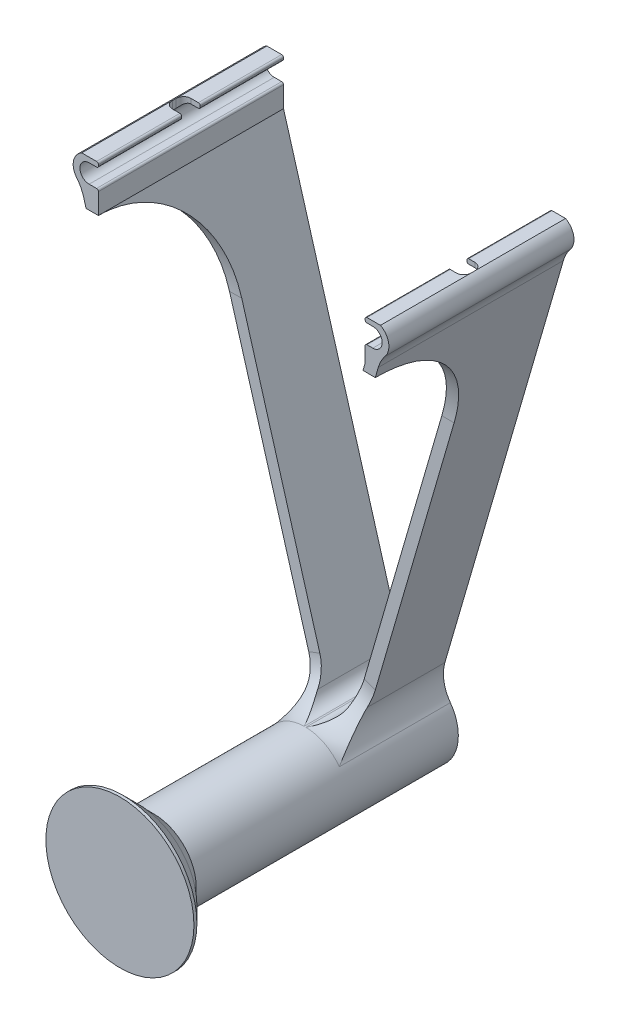
SolidWorks part; units mm, degrees
ref_plane "Front Plane" through (0, 0, 0) normal (0, 0, 1) x (1, 0, 0)
ref_plane "Top Plane" through (0, 0, 0) normal (0, 1, 0) x (1, 0, 0)
ref_plane "Right Plane" through (0, 0, 0) normal (1, 0, 0) x (0, 0, -1)
sketch "Sketch1" plane through (0, 0, 0) normal (0, 0, 1) x (1, 0, 0)
  line L6 (-35.807, 65.4375) -> (-21.497, 16.2472)
  line L8 (36.2341, 66.9059) -> (21.497, 16.2472)
  line L17 (39.7899, 67.7154) -> (18.5233, -5.3886)
  line L18 (-39.8147, 67.8005) -> (-18.5233, -5.3886)
  line L34 (-39.8353, 77.8524) -> (-36.807, 77.8524)
  line L35 (39.8353, 77.8524) -> (40.3798, 77.8524)
  line L36 (-39.8353, 77.8524) -> (-40.307, 77.8524)
  line L40 (36.2341, 77.0752) -> (36.2341, 77.3524)
  line L42 (36.2341, 70.9868) -> (36.2341, 66.9059)
  line L43 (36.7341, 77.8524) -> (39.8353, 77.8524)
  line L45 (-38.307, 71.5312) -> (-36.307, 71.5312)
  line L46 (-35.807, 71.0312) -> (-35.807, 65.4375)
  line L47 (-36.807, 77.8524) -> (-36.307, 77.8524)
  line L48 (-35.807, 77.3524) -> (-35.807, 77.0313)
  line L49 (38.307, 71.4868) -> (36.7341, 71.4868)
  line L50 (-38.307, 76.5313) -> (-36.307, 76.5313)
  line L51 (38.307, 76.5752) -> (36.7341, 76.5752)
  line L52 (-21.497, 16.2472) -> (-4.158, -43.3559)
  line L53 (21.497, 16.2472) -> (4.158, -43.3559)
  line L56 (-18.5233, -5.3886) -> (-7.7737, -42.3405)
  line L57 (7.7737, -42.3405) -> (18.5233, -5.3886)
  arc A10 (-40.307, 77.8524) -> (-41.6546, 71.312) centre (-38.307, 74.0312) ccw
  arc A11 (41.6658, 71.2709) -> (40.3798, 77.8524) centre (38.307, 74.031) ccw
  arc A16 (41.6658, 71.2709) -> (39.7899, 67.7154) centre (49.3919, 64.9221) ccw
  arc A17 (-39.8147, 67.8005) -> (-41.6546, 71.312) centre (-49.4166, 65.0072) ccw
  arc A23 (36.2341, 77.3524) -> (36.7341, 77.8524) centre (36.7341, 77.3524) cw
  arc A24 (-38.307, 76.5313) -> (-38.307, 71.5312) centre (-38.307, 74.0312) ccw
  arc A25 (38.307, 71.4868) -> (38.307, 76.5752) centre (38.307, 74.031) ccw
  arc A26 (-36.307, 71.5312) -> (-35.807, 71.0312) centre (-36.307, 71.0312) cw
  arc A27 (36.7341, 71.4868) -> (36.2341, 70.9868) centre (36.7341, 70.9868) ccw
  arc A28 (36.7341, 76.5752) -> (36.2341, 77.0752) centre (36.7341, 77.0752) cw
  arc A29 (-36.307, 76.5313) -> (-35.807, 77.0313) centre (-36.307, 77.0313) ccw
  arc A30 (-36.307, 77.8524) -> (-35.807, 77.3524) centre (-36.307, 77.3524) cw
  arc A35 (-9.2613, -50.9783) -> (9.2613, -50.9783) centre (0, -57.6489) ccw
  arc A36 (0.2349, -46.2378) -> (-0.2349, -46.2378) centre (0, -57.6489) ccw
  arc A37 (7.7737, -42.3405) -> (9.2613, -50.9783) centre (17.3756, -45.1338) ccw
  arc A38 (-7.7737, -42.3405) -> (-9.2613, -50.9783) centre (-17.3756, -45.1338) cw
  arc A39 (4.158, -43.3559) -> (0.2349, -46.2378) centre (0.3172, -42.2386) cw
  arc A40 (-4.158, -43.3559) -> (-0.2349, -46.2378) centre (-0.3172, -42.2386) ccw
  point P0 (0, 0)
  point P2 (0, 77.0313)
  point P10 (42.5, 77.0313)
  point P16 (0, 77.0313)
  point P17 (-42.5, 77.0313)
  point P24 (0, 74.0312)
  point P32 (3.1881, -46.6897)
  point P57 (36.2341, 77.8524)
  point P58 (3.1881, -46.6897)
  dimension "D2" = 10
  dimension "D3" = 10
  dimension "D4" = 0.5
  dimension "D5" = 4
  dimension "D1" = 85
extrude "Boss-Extrude1" add sketch "Sketch1" along normal blind 50 contours L43 L35 A11 A16 L17 L57 A37 A35 A38 L56 L18 A17 A10 L36 L34 L47 A30 L48 A29 L50 A24 L45 A26 L46 L6 L52 A40 A36 A39 L53 L8 L42 A27 L49 A25 L51 A28 L40 A23
sketch "Sketch2" plane through (0, 0, 50) normal (0, 0, 1) x (1, 0, 0)
  circle A0 centre (0, -57.6489) radius 11.4136
extrude "Boss-Extrude2" add sketch "Sketch2" along normal blind 25
sketch "Sketch3" plane through (0, 0, 50) normal (0, 0, 1) x (1, 0, 0)
  line L0 (7.7737, -42.3405) -> (39.7899, 67.7154) construction
  line L6 (36.2341, 66.9059) -> (4.158, -43.3559) construction
  line L7 (-4.158, -43.3559) -> (-35.807, 65.4375) construction
  line L8 (35.6637, 64.945) -> (38.9774, 64.9221)
  line L13 (-39.8147, 67.8005) -> (-7.7737, -42.3405) construction
  line L14 (7.7737, -42.3405) -> (38.9774, 64.9221)
  line L20 (35.6637, 64.945) -> (4.158, -43.3559)
  line L21 (-4.158, -43.3559) -> (-35.807, 65.4375)
  line L27 (-39.1273, 65.4375) -> (-7.7737, -42.3405)
  line L28 (-35.807, 65.4375) -> (-39.1273, 65.4375)
  arc A0 (9.2613, -50.9783) -> (0.2349, -46.2378) centre (0, -57.6489) ccw construction
  arc A1 (7.7737, -42.3405) -> (9.2613, -50.9783) centre (17.3756, -45.1338) ccw construction
  arc A8 (0.2349, -46.2378) -> (4.158, -43.3559) centre (0.3172, -42.2386) ccw construction
  arc A9 (-0.2349, -46.2378) -> (-9.2613, -50.9783) centre (0, -57.6489) ccw construction
  arc A10 (-4.158, -43.3559) -> (-0.2349, -46.2378) centre (-0.3172, -42.2386) ccw construction
  arc A17 (-9.2613, -50.9783) -> (-7.7737, -42.3405) centre (-17.3756, -45.1338) ccw construction
  arc A18 (9.2613, -50.9783) -> (0.2349, -46.2378) centre (0, -57.6489) ccw
  arc A19 (7.7737, -42.3405) -> (9.2613, -50.9783) centre (17.3756, -45.1338) ccw
  arc A26 (0.2349, -46.2378) -> (4.158, -43.3559) centre (0.3172, -42.2386) ccw
  arc A27 (-0.2349, -46.2378) -> (-9.2613, -50.9783) centre (0, -57.6489) ccw
  arc A28 (-4.158, -43.3559) -> (-0.2349, -46.2378) centre (-0.3172, -42.2386) ccw
  arc A35 (-9.2613, -50.9783) -> (-7.7737, -42.3405) centre (-17.3756, -45.1338) ccw
extrude "Cut-Extrude1" cut sketch "Sketch3" against normal blind 30
fillet "Fillet1" radius 10 2 edges at (5.3068, -47.5441, 20) (-5.3068, -47.5441, 20)
fillet "Fillet2" radius 30 2 edges at (37.3205, 64.9336, 20) (-37.4671, 65.4375, 20)
sketch "Sketch4" plane through (0, 0, 75) normal (0, 0, 1) x (1, 0, 0)
  circle A0 centre (0, -57.6489) radius 20
extrude "Boss-Extrude3" add sketch "Sketch4" along normal blind 5
chamfer "Chamfer1" distance 4.2 angle 45 2 edges at (20, -57.6489, 75) (11.4136, -57.6489, 75)
sketch "Sketch5" plane through (0, 77.8524, 0) normal (0, 1, 0) x (1, 0, 0)
  line L0 (-35.807, -50) -> (-35.807, 0) construction
  line L1 (-35.807, -22.5) -> (-40.307, -22.5)
  line L3 (-35.807, -27.5) -> (-40.307, -27.5)
  line L4 (-40.307, -22.5) -> (-40.307, -27.5)
  line L5 (-35.807, -25) -> (-40.307, -27.5) construction
  line L6 (-35.807, -25) -> (-40.307, -22.5) construction
  line L7 (-40.307, -50) -> (-40.307, 0) construction
  line L8 (36.7341, -50) -> (36.7341, 0) construction
  line L9 (36.2341, -22.5) -> (40.3798, -22.5)
  line L11 (36.2341, -27.5) -> (40.3798, -27.5)
  line L12 (40.3798, -22.5) -> (40.3798, -27.5)
  line L15 (40.3798, -50) -> (40.3798, 0) construction
  line L16 (-35.807, -22.5) -> (-35.807, -27.5)
  line L18 (36.2341, -22.5) -> (36.2341, -27.5)
  line L19 (36.2341, -50) -> (36.2341, 0) construction
  point P0 (-35.807, -25)
  point P9 (36.7341, -25)
extrude "Cut-Extrude2" cut sketch "Sketch5" against normal blind 4
fillet "Fillet3" radius 2 4 edges at (-40.307, 76.6918, 22.5) (-40.307, 76.6918, 27.5) (40.3798, 76.6793, 22.5) (40.3798, 76.6793, 27.5)
